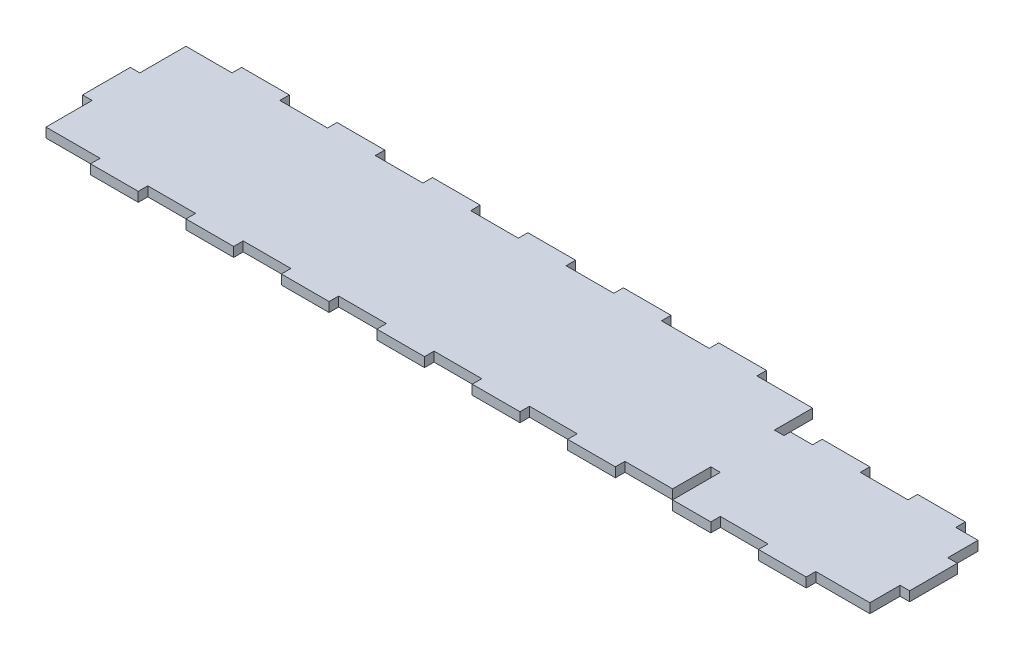
SolidWorks part; units mm, degrees
ref_plane "Alzado" through (0, 0, 0) normal (0, 0, 1) x (1, 0, 0)
ref_plane "Planta" through (0, 0, 0) normal (0, 1, 0) x (1, 0, 0)
ref_plane "Vista lateral" through (0, 0, 0) normal (1, 0, 0) x (0, 0, -1)
sketch "Croquis1" plane through (0, 0, 0) normal (0, 1, 0) x (1, 0, 0)
  line L1 (17.5, 50) -> (32.5, 50)
  line L2 (197, 3) -> (200, 3)
  line L3 (20, 0) -> (35, 0)
  line L4 (265, 12.5) -> (265, 27.5)
  line L5 (255, 40) -> (240, 40)
  line L6 (0, 25) -> (0, 32.5)
  line L7 (0, 32.5) -> (3, 32.5)
  line L8 (3, 32.5) -> (3, 47)
  line L9 (200, 15) -> (203, 15)
  line L10 (107.5, 47) -> (92.5, 47)
  line L11 (92.5, 47) -> (92.5, 50)
  line L12 (92.5, 50) -> (77.5, 50)
  line L13 (77.5, 50) -> (77.5, 47)
  line L14 (77.5, 47) -> (62.5, 47)
  line L15 (62.5, 47) -> (62.5, 50)
  line L16 (62.5, 50) -> (47.5, 50)
  line L17 (47.5, 50) -> (47.5, 47)
  line L18 (47.5, 47) -> (32.5, 47)
  line L19 (32.5, 47) -> (32.5, 50)
  line L20 (32.5, 50) -> (17.5, 50)
  line L21 (17.5, 50) -> (17.5, 47)
  line L22 (17.5, 47) -> (3, 47)
  line L23 (182.5, 47) -> (197, 47)
  line L24 (182.5, 50) -> (182.5, 47)
  line L25 (167.5, 47) -> (167.5, 50)
  line L26 (152.5, 47) -> (167.5, 47)
  line L27 (152.5, 50) -> (152.5, 47)
  line L28 (137.5, 47) -> (137.5, 50)
  line L29 (122.5, 47) -> (137.5, 47)
  line L30 (122.5, 50) -> (122.5, 47)
  line L31 (107.5, 47) -> (107.5, 50)
  line L32 (0, 25) -> (0, 17.5)
  line L33 (203, 15) -> (203, 0)
  line L34 (0, 17.5) -> (3, 17.5)
  line L35 (3, 17.5) -> (3, 3)
  line L36 (225, 40) -> (210, 40)
  line L37 (140, 3) -> (125, 3)
  line L38 (125, 3) -> (125, 0)
  line L39 (125, 0) -> (110, 0)
  line L40 (110, 0) -> (110, 3)
  line L41 (110, 3) -> (95, 3)
  line L42 (95, 3) -> (95, 0)
  line L43 (95, 0) -> (80, 0)
  line L44 (80, 0) -> (80, 3)
  line L45 (80, 3) -> (65, 3)
  line L46 (65, 3) -> (65, 0)
  line L47 (65, 0) -> (50, 0)
  line L48 (50, 0) -> (50, 3)
  line L49 (50, 3) -> (35, 3)
  line L50 (35, 3) -> (35, 0)
  line L51 (35, 0) -> (20, 0)
  line L52 (20, 0) -> (20, 3)
  line L53 (20, 3) -> (3, 3)
  line L54 (245, 3) -> (262, 3)
  line L55 (245, 0) -> (245, 3)
  line L56 (230, 3) -> (230, 0)
  line L57 (215, 3) -> (230, 3)
  line L58 (215, 0) -> (215, 3)
  line L60 (185, 3) -> (197, 3)
  line L61 (185, 0) -> (185, 3)
  line L62 (170, 3) -> (170, 0)
  line L63 (155, 3) -> (170, 3)
  line L64 (155, 0) -> (155, 3)
  line L65 (140, 3) -> (140, 0)
  line L66 (255, 40) -> (240, 40)
  line L67 (200, 35) -> (203, 35)
  line L68 (225, 37) -> (240, 37)
  line L69 (240, 37) -> (240, 40)
  line L70 (240, 40) -> (255, 40)
  line L71 (255, 40) -> (255, 37)
  line L72 (255, 37) -> (262, 37)
  line L73 (210, 37) -> (203, 37)
  line L74 (210, 40) -> (210, 37)
  line L75 (225, 37) -> (225, 40)
  line L76 (203, 35) -> (203, 37)
  line L78 (265, 20) -> (265, 27.5)
  line L79 (265, 27.5) -> (262, 27.5)
  line L80 (262, 27.5) -> (262, 37)
  line L81 (265, 20) -> (265, 12.5)
  line L82 (265, 12.5) -> (262, 12.5)
  line L83 (262, 12.5) -> (262, 3)
  line L85 (197, 47) -> (200, 47)
  line L87 (200, 35) -> (200, 37)
  line L89 (200, 15) -> (200, 3)
  line L90 (0, 17.5) -> (0, 32.5)
  line L91 (50, 0) -> (65, 0)
  line L92 (80, 0) -> (95, 0)
  line L93 (110, 0) -> (125, 0)
  line L94 (140, 0) -> (155, 0)
  line L95 (170, 0) -> (185, 0)
  line L96 (203, 0) -> (215, 0)
  line L97 (230, 0) -> (245, 0)
  line L98 (167.5, 50) -> (182.5, 50)
  line L99 (137.5, 50) -> (152.5, 50)
  line L100 (47.5, 50) -> (62.5, 50)
  line L101 (77.5, 50) -> (92.5, 50)
  line L102 (107.5, 50) -> (122.5, 50)
  line L103 (200, 47) -> (200, 37)
  dimension "D4" = 3
  dimension "D5" = 7.5
  dimension "D6" = 3
  dimension "D9" = 15
  dimension "D10" = 15
  dimension "D11" = 15
  dimension "D12" = 15
  dimension "D13" = 15
  dimension "D14" = 7.5
  dimension "D17" = 15
  dimension "D18" = 15
  dimension "D19" = 15
  dimension "D20" = 15
  dimension "D21" = 15
  dimension "D22" = 15
  dimension "D23" = 15
  dimension "D26" = 15
  dimension "D27" = 7.5
  dimension "D28" = 3
  dimension "D29" = 7.5
extrude "Saliente-Extruir1" add sketch "Croquis1" along normal blind 3 contours L102 L31 L10 L11 L12 L13 L14 L15 L16 L17 L18 L19 L1 L21 L22 L8 L7 L6 L32 L34 L35 L53 L52 L3 L50 L49 L48 L47 L46 L45 L44 L43 L42 L41 L40 L39 L38 L37 L65 L94 L64 L63 L62 L95 L61 L60 L89 L96 region at (126.9201, 0, -24.0513)
